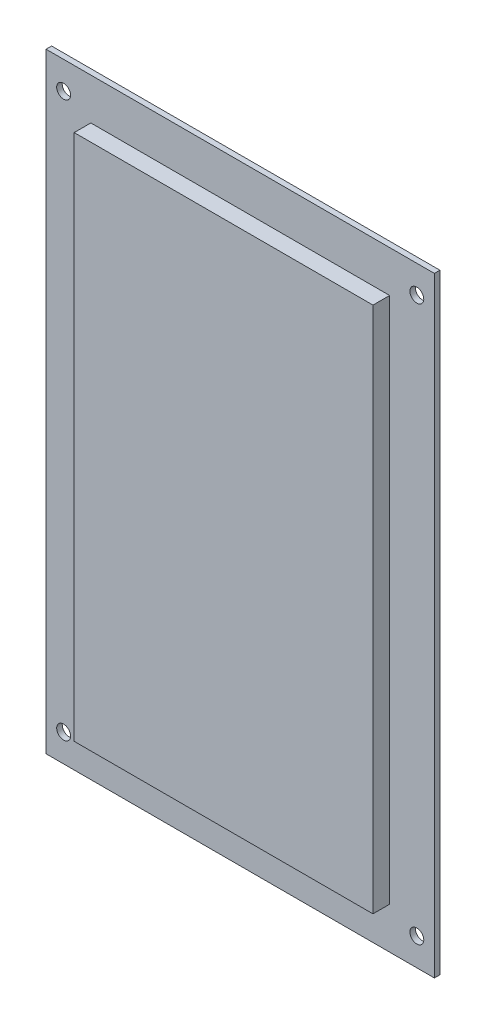
SolidWorks part; units mm, degrees
ref_plane "Front Plane" through (0, 0, 0) normal (0, 0, 1) x (1, 0, 0)
ref_plane "Top Plane" through (0, 0, 0) normal (0, 1, 0) x (1, 0, 0)
ref_plane "Right Plane" through (0, 0, 0) normal (1, 0, 0) x (0, 0, -1)
sketch "Sketch2" plane through (0, 0, 0) normal (0, 0, 1) x (1, 0, 0)
  line L0 (-20.017, 37.185) -> (33.843, 37.185) construction
  line L1 (-20.017, 43.585) -> (33.843, 43.585)
  line L2 (-20.017, 43.585) -> (-20.017, -51.455)
  line L3 (-20.017, -51.455) -> (33.843, -51.455)
  line L4 (33.843, 43.585) -> (33.843, -51.455)
  line L5 (-20.017, -41.055) -> (33.843, -41.055) construction
  line L6 (6.913, 43.585) -> (6.913, -51.455) construction
  dimension "D1" = 95.04
  dimension "D2" = 53.86
  dimension "D3" = 6.4
  dimension "D4" = 10.4
extrude "Boss-Extrude1" add sketch "Sketch2" along normal blind 3
sketch "Sketch3" plane through (0, 0, 0) normal (0, 0, -1) x (-1, 0, 0)
  line L0 (-6.913, -51.455) -> (-6.913, 43.585) construction
  line L1 (20.017, -51.455) -> (-33.843, -51.455) construction
  line L2 (-33.843, 43.585) -> (20.017, 43.585) construction
  line L3 (-33.843, -3.935) -> (20.017, -3.935) construction
  line L4 (-33.843, -51.455) -> (-33.843, 43.585) construction
  line L5 (20.017, 43.585) -> (20.017, -51.455) construction
  line L7 (-41.913, 51.065) -> (28.087, 51.065)
  line L8 (-41.913, 51.065) -> (-41.913, -58.935)
  line L9 (-41.913, -58.935) -> (28.087, -58.935)
  line L10 (28.087, 51.065) -> (28.087, -58.935)
  line L11 (-41.913, 51.065) -> (28.087, -58.935) construction
  line L12 (-41.913, -58.935) -> (28.087, 51.065) construction
  circle A0 centre (24.9229, 46.0929) radius 1.25
  circle A1 centre (24.9229, -53.9629) radius 1.25
  circle A2 centre (-38.7489, 46.0929) radius 1.25
  circle A3 centre (-38.7489, -53.9629) radius 1.25
  point P12 (-6.913, -3.935)
  dimension "D1" = 2.5
  dimension "D2" = 110
  dimension "D3" = 70
extrude "Boss-Extrude2" add sketch "Sketch3" along normal blind 1
